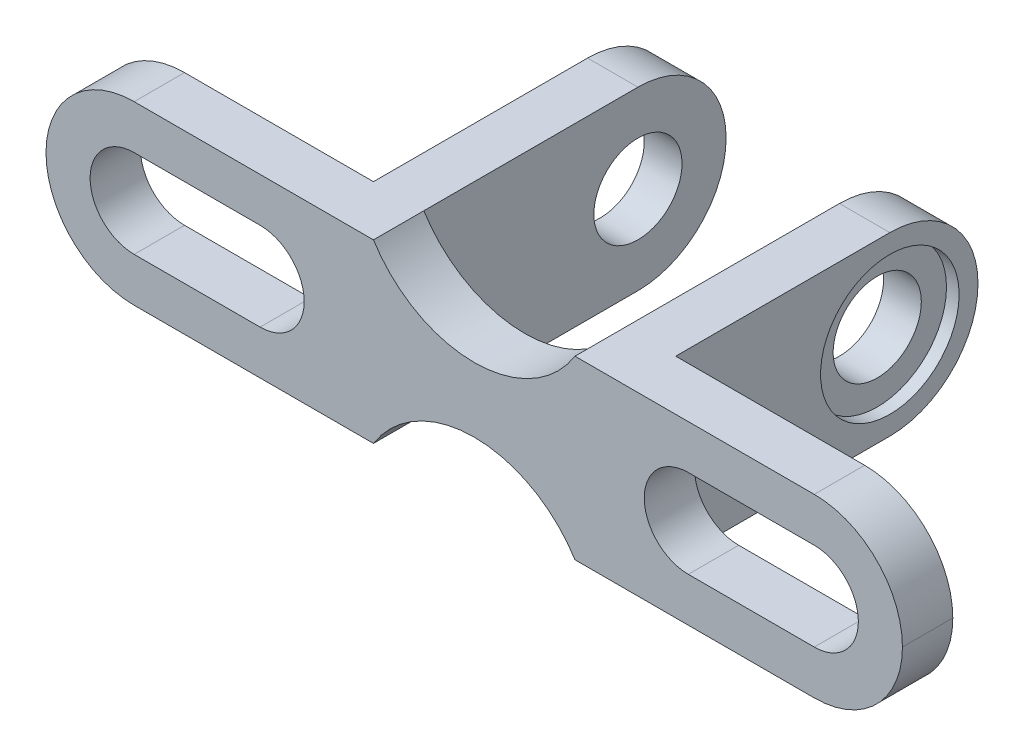
SolidWorks part; units mm, degrees
ref_plane "前视基准面" through (0, 0, 0) normal (0, 0, 1) x (1, 0, 0)
ref_plane "上视基准面" through (0, 0, 0) normal (0, 1, 0) x (1, 0, 0)
ref_plane "右视基准面" through (0, 0, 0) normal (1, 0, 0) x (0, 0, -1)
sketch "草图3" plane through (0, 0, 0) normal (0, 0, 1) x (1, 0, 0)
  line L0 (-13.5, 0) -> (-8.5, 0) construction
  line L1 (-17, -3.5) -> (-4, -3.5)
  line L2 (-17, -3.5) -> (-17, 3.5)
  line L3 (-17, 3.5) -> (-4, 3.5)
  line L4 (17, -3.5) -> (17, 3.5)
  line L5 (-17, -3.5) -> (17, 3.5) construction
  line L6 (-17, 3.5) -> (17, -3.5) construction
  line L7 (-13.5, 1.75) -> (-8.5, 1.75)
  line L8 (-13.5, -1.75) -> (-8.5, -1.75)
  line L9 (0, 3.5) -> (0, -3.5) construction
  line L10 (13.5, 0) -> (8.5, 0) construction
  line L11 (13.5, 1.75) -> (8.5, 1.75)
  line L12 (13.5, -1.75) -> (8.5, -1.75)
  line L13 (-13, -11.2774) -> (13, -11.2774) construction
  line L14 (0, 6) -> (0, 0) construction
  line L15 (-6.75, 0) -> (6.75, 0) construction
  line L16 (4, -3.5) -> (17, -3.5)
  line L17 (4, 3.5) -> (17, 3.5)
  arc A0 (-13.5, 1.75) -> (-13.5, -1.75) centre (-13.5, 0) ccw
  arc A1 (-8.5, -1.75) -> (-8.5, 1.75) centre (-8.5, 0) ccw
  arc A2 (13.5, 1.75) -> (13.5, -1.75) centre (13.5, 0) cw
  arc A3 (8.5, -1.75) -> (8.5, 1.75) centre (8.5, 0) cw
  arc A4 (-4, 3.5) -> (4, 3.5) centre (0, 6) ccw
  arc A5 (-4, -3.5) -> (4, -3.5) centre (0, -6) cw
  point P0 (0, 0)
  point P8 (-11, 0)
  point P17 (11, 0)
  point P24 (0, -11.2774)
  dimension "D3" = 1.75
  dimension "D8" = 8
  dimension "D1" = 34
  dimension "D2" = 7
  dimension "D4" = 3.5
  dimension "D5" = 26
  dimension "D6" = 5
  dimension "D7" = 6
extrude "凸台-拉伸2" add sketch "草图3" along normal blind 2
sketch "草图4" plane through (0, 0, 0) normal (0, 0, -1) x (-1, 0, 0)
  line L0 (0, 3.5) -> (0, -3.5) construction
  line L1 (-6, 3.5) -> (-4, 3.5)
  line L2 (-6, 3.5) -> (-6, -3.5)
  line L3 (-6, -3.5) -> (-4, -3.5)
  line L4 (-4, 3.5) -> (-4, -3.5)
  line L5 (-6, 3.5) -> (-4, -3.5) construction
  line L6 (-6, -3.5) -> (-4, 3.5) construction
  line L7 (6, -3.5) -> (4, 3.5) construction
  line L8 (6, 3.5) -> (4, -3.5) construction
  line L9 (4, 3.5) -> (4, -3.5)
  line L10 (6, -3.5) -> (4, -3.5)
  line L11 (6, 3.5) -> (6, -3.5)
  line L12 (6, 3.5) -> (4, 3.5)
  line L13 (-4, -3.5) -> (-17, -3.5) construction
  point P0 (-5, 0)
  point P14 (5, 0)
  dimension "D1" = 2
  dimension "D2" = 8
extrude "凸台-拉伸3" add sketch "草图4" along normal blind 12
fillet "圆角1" radius 3.5 4 edges at (-5, -3.5, -12) (-5, 3.5, -12) (5, -3.5, -12) (5, 3.5, -12)
sketch "草图5" plane through (6, 0, 0) normal (1, 0, 0) x (0, 0, -1)
  line L0 (8.5, 3.5) -> (8.5, -3.5) construction
  circle A0 centre (8.5, 0) radius 1.75
  dimension "D1" = 3.5
extrude "切除-拉伸1" cut sketch "草图5" against normal through all
fillet "圆角2" radius 3.5 4 edges at (17, -3.5, 1) (17, 3.5, 1) (-17, -3.5, 1) (-17, 3.5, 1)
sketch "草图6" plane through (6, 0, 0) normal (1, 0, 0) x (0, 0, -1)
  circle A0 centre (8.5, 0) radius 2.75
  circle A1 centre (8.5, 0) radius 1.75 construction
  dimension "D1" = 1
extrude "切除-拉伸2" cut sketch "草图6" against normal blind 0.5
sketch "草图7" plane through (-6, 0, 0) normal (-1, 0, 0) x (0, 0, 1)
  circle A0 centre (-8.5, 0) radius 2.75
  circle A1 centre (-8.5, 0) radius 1.75 construction
  dimension "D1" = 1
extrude "切除-拉伸3" cut sketch "草图7" against normal blind 0.5
